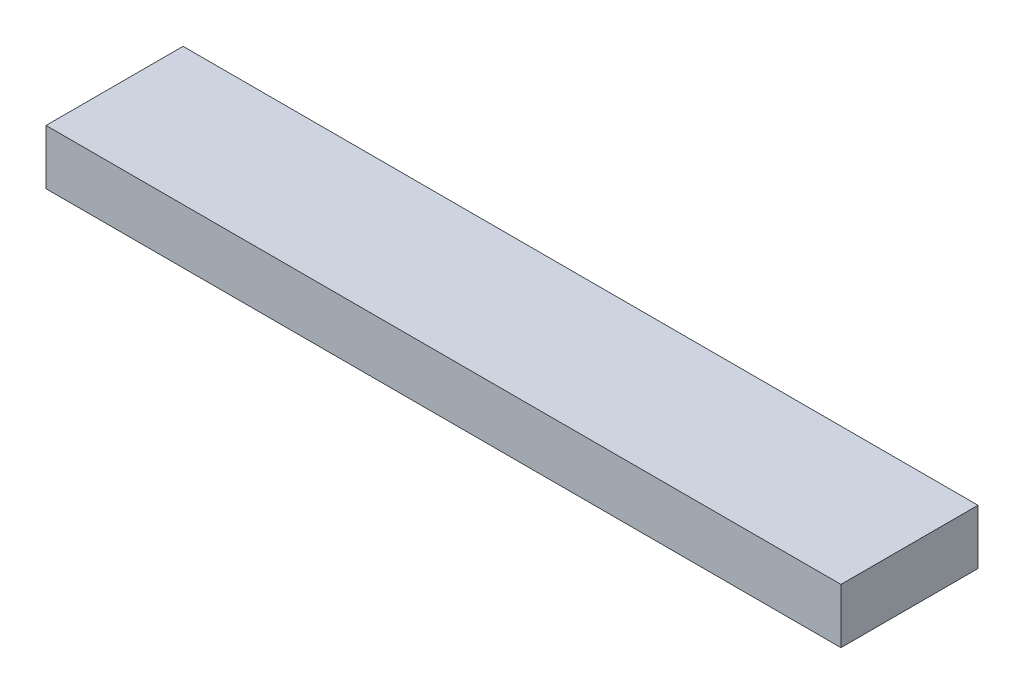
SolidWorks part; units mm, degrees
material "Сосна"
ref_plane "Спереди" through (0, 0, 0) normal (0, 0, 1) x (1, 0, 0)
ref_plane "Сверху" through (0, 0, 0) normal (0, 1, 0) x (1, 0, 0)
ref_plane "Справа" through (0, 0, 0) normal (1, 0, 0) x (0, 0, -1)
sketch "Эскиз1" plane through (0, 0, 0) normal (0, 1, 0) x (1, 0, 0)
  line L1 (0, 0) -> (145, 0)
  line L2 (0, 0) -> (0, 25)
  line L3 (0, 25) -> (145, 25)
  line L4 (145, 0) -> (145, 25)
  dimension "D1" = 25
  dimension "D2" = 145
extrude "Бобышка-Вытянуть1" add sketch "Эскиз1" along normal blind 10
